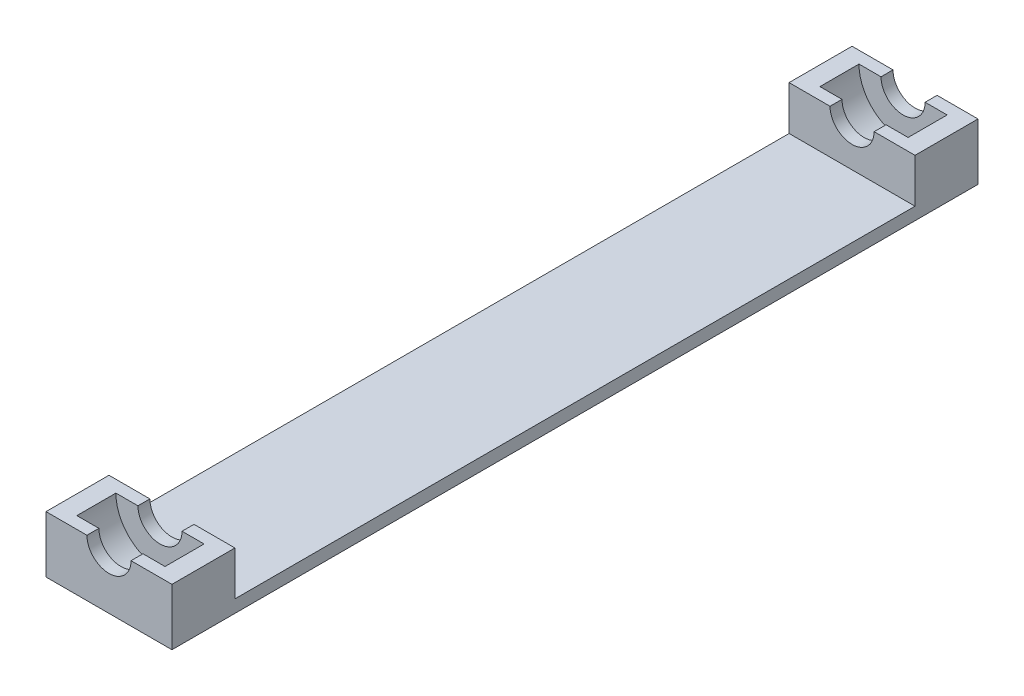
SolidWorks part; units mm, degrees
ref_plane "Front Plane" through (0, 0, 0) normal (0, 0, 1) x (1, 0, 0)
ref_plane "Top Plane" through (0, 0, 0) normal (0, 1, 0) x (1, 0, 0)
ref_plane "Right Plane" through (0, 0, 0) normal (1, 0, 0) x (0, 0, -1)
sketch "Sketch1" plane through (0, 0, 0) normal (1, 0, 0) x (0, 0, -1)
  line L0 (0, 21.9578) -> (0, -21.9578) construction
  line L1 (-32, 0.5) -> (32, 0.5)
  line L2 (-32, 0.5) -> (-32, -0.5)
  line L3 (-32, -0.5) -> (32, -0.5)
  line L4 (32, 0.5) -> (32, -0.5)
  line L5 (0, -0.5) -> (0, 0.5) construction
  line L6 (-32, 0) -> (32, 0) construction
  line L7 (27, 4) -> (32, 4)
  line L8 (27, 4) -> (27, 0.5)
  line L9 (27, 0.5) -> (32, 0.5)
  line L10 (32, 4) -> (32, 0.5)
  line L11 (29.5, 0.5) -> (29.5, 4) construction
  line L12 (27, 2.25) -> (32, 2.25) construction
  line L13 (-32, 4) -> (-32, 0.5)
  line L14 (-27, 4) -> (-32, 4)
  line L15 (-27, 4) -> (-27, 0.5)
  point P0 (0, 0)
  point P4 (0, 0)
  point P5 (29.5, 2.25)
  point P9 (0, 0)
  point P12 (0, 0)
  dimension "D1" = 64
  dimension "D2" = 1
  dimension "D3" = 3.5
  dimension "D4" = 5
extrude "Boss-Extrude1" add sketch "Sketch1" along normal blind 10 contours L15 L14 L13 L1 | L10 L7 L8 L1 | L1 L4 L3 L2 region at (0, 2.25, 29.5) region at (0, 2.25, -29.5)
ref_plane "Plane1" through (0, 0, 29.5) normal (0, 0, 1) x (1, 0, 0)
sketch "Sketch2" plane through (0, 0, 29.5) normal (0, 0, 1) x (1, 0, 0)
  line L1 (0, 4) -> (10, 4) construction
  line L2 (0, 4) -> (0, -0.5) construction
  line L3 (0, -0.5) -> (10, -0.5) construction
  line L4 (10, 4) -> (10, -0.5) construction
  line L5 (5, -0.5) -> (5, 4) construction
  line L6 (0, 1.75) -> (10, 1.75) construction
  circle A1 centre (5, 4) radius 3.5
  circle A2 centre (5, 4) radius 1.75
  point P0 (5, 1.75)
  point P6 (0, 0)
  dimension "D1" = 7
  dimension "D2" = 3.5
extrude "Cut-Extrude1" cut sketch "Sketch2" against normal mid plane 3.1
ref_plane "Plane3" through (0, 0, -29.5) normal (0, 0, 1) x (1, 0, 0)
ref_plane "Plane4" through (0, 0, 0) normal (0, 0, 1) x (1, 0, 0)
extrude "Cut-Extrude2" cut sketch "Sketch2<2>" against normal mid plane 13.2 contours A2 region at (5, 4, 29.5)
sketch "Sketch2<2>" plane through (0, 0, 29.5) normal (0, 0, 1) x (1, 0, 0) same geometry as "Sketch2"
mirror "Mirror1" about plane through (0, 0, 0) normal (0, 0, 1) of "Cut-Extrude1"
mirror "Mirror2" about plane through (0, 0, 0) normal (0, 0, 1) of "Cut-Extrude2"
